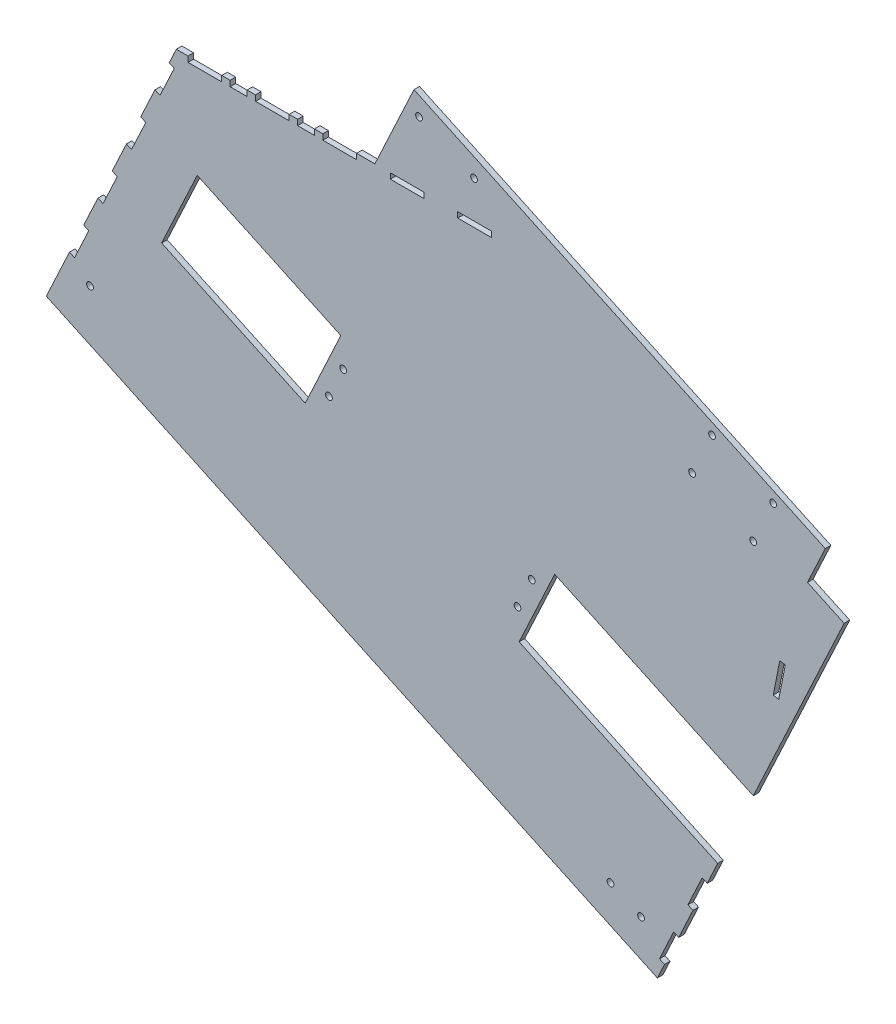
SolidWorks part; units mm, degrees
material "Balsa"
ref_plane "Front Plane" through (0, 0, 0) normal (0, 0, 1) x (1, 0, 0)
ref_plane "Top Plane" through (0, 0, 0) normal (0, 1, 0) x (1, 0, 0)
ref_plane "Right Plane" through (0, 0, 0) normal (1, 0, 0) x (0, 0, -1)
sketch "Sketch1" plane through (0, 0, 0) normal (0, 0, 1) x (1, 0, 0)
  line L0 (-255.2098, 12.6381) -> (-137.4275, 12.6381)
  line L1 (-137.4275, 12.6381) -> (-114.243, 62.3574)
  line L2 (-114.243, 62.3574) -> (129.7831, -51.4338)
  line L3 (129.7831, -51.4338) -> (119.2177, -74.0915)
  line L4 (119.2177, -74.0915) -> (140.969, -84.2344)
  line L5 (140.969, -84.2344) -> (30.1585, -321.8683)
  line L6 (30.1585, -321.8683) -> (-332.3646, -152.8209)
  line L7 (-332.3646, -152.8209) -> (-255.2098, 12.6381)
  line L9 (-332.3646, -152.8209) -> (-261.0998, 0.0069) construction
  line L10 (30.1585, -321.8683) -> (-332.3646, -152.8209) construction
  line L11 (140.969, -84.2344) -> (30.1585, -321.8683) construction
  line L12 (-189.2372, 97.3278) -> (129.7831, -51.4338) construction
  line L13 (119.2177, -74.0915) -> (140.969, -84.2344) construction
  line L14 (129.7831, -51.4338) -> (119.2177, -74.0915) construction
  circle A0 centre (87.0035, -69.0002) radius 2
  circle A1 centre (98.8369, -43.6236) radius 2
  circle A2 centre (62.5845, -26.7189) radius 2
  circle A3 centre (50.7512, -52.0955) radius 2
  circle A4 centre (2.3586, -286.8374) radius 2
  circle A5 centre (-306.4229, -134.5749) radius 2
  circle A6 centre (20.4847, -295.2897) radius 2
  circle A7 centre (2.3586, -286.8374) radius 2 construction
  circle A8 centre (20.4847, -295.2897) radius 2 construction
  dimension "D1" = 4
  dimension "D2" = 4
  dimension "D3" = 4
  dimension "D4" = 4
  dimension "D7" = 4
  dimension "D5" = 27.5
  dimension "D6" = 15.8
extrude "Boss-Extrude1" add sketch "Sketch1" along normal up to surface (3.3 mm away)
sketch "Sketch2" plane through (0, 0, 0) normal (0, 0, -1) x (-1, 0, 0)
  line L0 (114.243, 62.3574) -> (137.4275, 12.6381) construction
  line L1 (-129.7831, -51.4338) -> (114.243, 62.3574) construction
  circle A0 centre (78.5916, 34.6991) radius 2
  circle A1 centre (111.2187, 49.9134) radius 2
  dimension "D1" = 4
  dimension "D2" = 4
  dimension "D3" = 8
  dimension "D4" = 36
  dimension "D5" = 10
  dimension "D6" = 10
extrude "Cut-Extrude1" cut sketch "Sketch2" against normal through all
sketch "Sketch5" plane through (0, 0, 3.3) normal (0, 0, 1) x (1, 0, 0)
  line L0 (65.9543, -245.104) -> (-51.8657, -190.1636)
  line L1 (140.969, -84.2344) -> (30.1585, -321.8683) construction
  line L2 (-51.8657, -190.1636) -> (-30.7348, -144.8482)
  line L3 (-30.7348, -144.8482) -> (87.0852, -199.7886)
  line L4 (87.0852, -199.7886) -> (65.9543, -245.104)
  line L5 (119.2177, -74.0915) -> (140.969, -84.2344) construction
  dimension "D1" = 130
  dimension "D2" = 127.5
  dimension "D3" = 50
extrude "Cut-Extrude2" cut sketch "Sketch5" against normal blind 10
sketch "Sketch6" plane through (0, 0, 3.3) normal (0, 0, 1) x (1, 0, 0)
  line L0 (-178.7488, -130.9971) -> (-157.6179, -85.6817)
  line L1 (-157.6179, -85.6817) -> (-242.8108, -45.9555)
  line L2 (-242.8108, -45.9555) -> (-263.9417, -91.2709)
  line L3 (-263.9417, -91.2709) -> (-178.7488, -130.9971)
  line L5 (87.0852, -199.7886) -> (-30.7348, -144.8482) construction
  line L6 (-51.8657, -190.1636) -> (65.9543, -245.104) construction
  line L7 (-332.3646, -152.8209) -> (-255.2098, 12.6381) construction
  line L8 (129.7831, -51.4338) -> (119.2177, -74.0915) construction
  dimension "D1" = 130
  dimension "D2" = 340
extrude "Cut-Extrude3" cut sketch "Sketch6" against normal blind 10
sketch "Sketch7" plane through (0, 0, 3.3) normal (0, 0, 1) x (1, 0, 0)
  circle A0 centre (-52.7985, -172.5711) radius 2
  circle A1 centre (-44.3462, -154.4449) radius 2
  circle A2 centre (-164.6725, -120.4034) radius 2
  circle A3 centre (-156.2202, -102.2772) radius 2
  circle A4 centre (-52.7985, -172.5711) radius 2 construction
  circle A5 centre (-44.3462, -154.4449) radius 2 construction
  circle A6 centre (-164.6725, -120.4034) radius 2 construction
  circle A7 centre (-156.2202, -102.2772) radius 2 construction
extrude "Cut-Extrude4" cut sketch "Sketch7" against normal blind 10
sketch "Sketch8" plane through (0, 0, 3.3) normal (0, 0, 1) x (1, 0, 0)
  line L0 (-255.2098, 12.6381) -> (-137.4275, 12.6381) construction
  line L1 (-248.2814, 12.6381) -> (-228.2814, 12.6381)
  line L2 (-248.2814, 12.6381) -> (-248.2814, 9.3381)
  line L3 (-248.2814, 9.3381) -> (-228.2814, 9.3381)
  line L4 (-228.2814, 12.6381) -> (-228.2814, 9.3381)
  line L5 (-248.2814, 12.6381) -> (-228.2814, 9.3381) construction
  line L6 (-248.2814, 9.3381) -> (-228.2814, 12.6381) construction
  line L7 (-248.2814, 9.3381) -> (-248.2814, 12.6381) construction
  line L8 (-208.2814, 12.6381) -> (-188.2814, 12.6381)
  line L9 (-208.2814, 12.6381) -> (-208.2814, 9.3381)
  line L10 (-208.2814, 9.3381) -> (-188.2814, 9.3381)
  line L11 (-188.2814, 12.6381) -> (-188.2814, 9.3381)
  line L12 (-208.2814, 12.6381) -> (-188.2814, 9.3381) construction
  line L13 (-208.2814, 9.3381) -> (-188.2814, 12.6381) construction
  line L14 (-168.2814, 12.6381) -> (-148.2814, 12.6381)
  line L15 (-168.2814, 12.6381) -> (-168.2814, 9.3381)
  line L16 (-168.2814, 9.3381) -> (-148.2814, 9.3381)
  line L17 (-148.2814, 12.6381) -> (-148.2814, 9.3381)
  line L18 (-168.2814, 12.6381) -> (-148.2814, 9.3381) construction
  line L19 (-168.2814, 9.3381) -> (-148.2814, 12.6381) construction
  line L20 (-128.2814, 12.6381) -> (-108.2814, 12.6381)
  line L21 (-128.2814, 12.6381) -> (-128.2814, 9.3381)
  line L22 (-128.2814, 9.3381) -> (-108.2814, 9.3381)
  line L23 (-108.2814, 12.6381) -> (-108.2814, 9.3381)
  line L24 (-128.2814, 12.6381) -> (-108.2814, 9.3381) construction
  line L25 (-128.2814, 9.3381) -> (-108.2814, 12.6381) construction
  line L26 (-88.2814, 12.6381) -> (-68.2814, 12.6381)
  line L27 (-88.2814, 12.6381) -> (-88.2814, 9.3381)
  line L28 (-88.2814, 9.3381) -> (-68.2814, 9.3381)
  line L29 (-68.2814, 12.6381) -> (-68.2814, 9.3381)
  line L30 (-88.2814, 12.6381) -> (-68.2814, 9.3381) construction
  line L31 (-88.2814, 9.3381) -> (-68.2814, 12.6381) construction
  point P4 (-238.2814, 10.9881)
  point P14 (-198.2814, 10.9881)
  point P19 (-158.2814, 10.9881)
  point P24 (-118.2814, 10.9881)
  point P30 (-78.2814, 10.9881)
  dimension "D1" = 20
  dimension "D2" = 3.3
  dimension "D3" = 5
extrude "Cut-Extrude5" cut sketch "Sketch8" against normal blind 10
sketch "Sketch9" plane through (0, 0, 3.3) normal (0, 0, 1) x (1, 0, 0)
  line L0 (-259.4359, 3.575) -> (-256.4451, 2.1804)
  line L1 (-332.3646, -152.8209) -> (-255.2098, 12.6381) construction
  line L2 (-256.4451, 2.1804) -> (-264.8975, -15.9458)
  line L3 (-264.8975, -15.9458) -> (-267.8883, -14.5511)
  line L4 (-267.8883, -14.5511) -> (-259.4359, 3.575)
  line L5 (-276.3407, -32.6773) -> (-273.3499, -34.0719)
  line L6 (-273.3499, -34.0719) -> (-281.8022, -52.1981)
  line L7 (-281.8022, -52.1981) -> (-284.793, -50.8035)
  line L8 (-284.793, -50.8035) -> (-276.3407, -32.6773)
  line L9 (-293.2454, -68.9296) -> (-290.2546, -70.3242)
  line L10 (-290.2546, -70.3242) -> (-298.707, -88.4504)
  line L11 (-298.707, -88.4504) -> (-301.6978, -87.0558)
  line L12 (-301.6978, -87.0558) -> (-293.2454, -68.9296)
  line L13 (-310.1501, -105.1819) -> (-307.1593, -106.5766)
  line L14 (-307.1593, -106.5766) -> (-315.6117, -124.7027)
  line L15 (-315.6117, -124.7027) -> (-318.6025, -123.3081)
  line L16 (-318.6025, -123.3081) -> (-310.1501, -105.1819)
  dimension "D1" = 3.3
  dimension "D2" = 20
  dimension "D3" = 10
  dimension "D4" = 4
extrude "Cut-Extrude6" cut sketch "Sketch9" against normal blind 10
sketch "Sketch10" plane through (0, 0, 3.3) normal (0, 0, 1) x (1, 0, 0)
  line L0 (-255.2098, 12.6381) -> (-223.2814, 12.6381) construction
  line L1 (-173.2814, 12.6381) -> (-183.2814, 12.6381)
  line L2 (-173.2814, 12.6381) -> (-173.2814, 9.3381)
  line L3 (-173.2814, 9.3381) -> (-183.2814, 9.3381)
  line L4 (-183.2814, 12.6381) -> (-183.2814, 9.3381)
  line L5 (-173.2814, 12.6381) -> (-183.2814, 9.3381) construction
  line L6 (-173.2814, 9.3381) -> (-183.2814, 12.6381) construction
  line L7 (-188.2814, 9.3381) -> (-188.2814, 12.6381) construction
  line L8 (-213.2814, 12.6381) -> (-223.2814, 12.6381)
  line L9 (-213.2814, 12.6381) -> (-213.2814, 9.3381)
  line L10 (-213.2814, 9.3381) -> (-223.2814, 9.3381)
  line L11 (-223.2814, 12.6381) -> (-223.2814, 9.3381)
  line L12 (-213.2814, 12.6381) -> (-223.2814, 9.3381) construction
  line L13 (-213.2814, 9.3381) -> (-223.2814, 12.6381) construction
  point P4 (-178.2814, 10.9881)
  point P15 (-218.2814, 10.9881)
  dimension "D1" = 10
  dimension "D2" = 3.3
  dimension "D3" = 5
  dimension "D4" = 2
extrude "Cut-Extrude7" cut sketch "Sketch10" against normal blind 3.3
sketch "Sketch11" plane through (0, 0, 3.3) normal (0, 0, 1) x (1, 0, 0)
  line L0 (34.3847, -312.8052) -> (31.3939, -311.4105)
  line L1 (65.9543, -245.104) -> (30.1585, -321.8683) construction
  line L2 (31.3939, -311.4105) -> (39.8463, -293.2844)
  line L3 (39.8463, -293.2844) -> (42.8371, -294.679)
  line L4 (42.8371, -294.679) -> (34.3847, -312.8052)
  line L5 (30.1585, -321.8683) -> (-332.3646, -152.8209) construction
  line L6 (51.2895, -276.5529) -> (48.2986, -275.1582)
  line L7 (48.2986, -275.1582) -> (56.751, -257.0321)
  line L8 (56.751, -257.0321) -> (59.7418, -258.4267)
  line L9 (59.7418, -258.4267) -> (51.2895, -276.5529)
  dimension "D1" = 3.3
  dimension "D2" = 20
  dimension "D3" = 10
  dimension "D4" = 2
extrude "Cut-Extrude8" cut sketch "Sketch11" against normal blind 3.3
sketch "Sketch12" plane through (0, 0, 0) normal (0, 0, -1) x (-1, 0, 0)
  line L0 (-102.7901, -122.4718) -> (-98.923, -142.0944)
  line L1 (-102.7901, -122.4718) -> (-106.0279, -123.1099)
  line L2 (-98.923, -142.0944) -> (-102.1607, -142.7325)
  line L3 (-106.0279, -123.1099) -> (-102.1607, -142.7325)
  line L4 (-119.2177, -74.0915) -> (-140.969, -84.2344) construction
  line L6 (-93.7982, -185.1655) -> (-102.1607, -142.7325) construction
  dimension "D1" = 50
  dimension "D2" = 3.3
  dimension "D3" = 20
extrude "Cut-Extrude9" cut sketch "Sketch12" against normal blind 3.3
